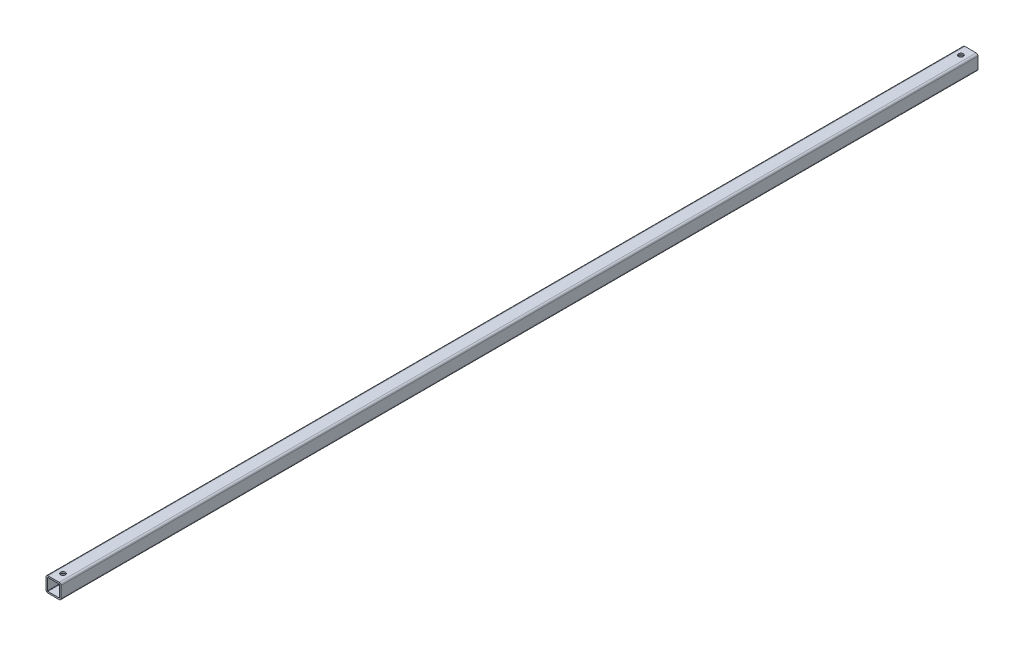
SolidWorks part; units mm, degrees
material "6063-T4"
ref_plane "Front Plane" through (0, 0, 0) normal (0, 0, 1) x (1, 0, 0)
ref_plane "Top Plane" through (0, 0, 0) normal (0, 1, 0) x (1, 0, 0)
ref_plane "Right Plane" through (0, 0, 0) normal (1, 0, 0) x (0, 0, -1)
sketch "Sketch1" plane through (0, 0, 0) normal (0, 0, 1) x (1, 0, 0)
  line L1 (7.5, -10) -> (-7.5, -10)
  line L2 (10, -7.5) -> (10, 7.5)
  line L3 (7.5, 10) -> (-7.5, 10)
  line L4 (-10, -7.5) -> (-10, 7.5)
  line L5 (10, -10) -> (-10, 10) construction
  line L6 (10, 10) -> (-10, -10) construction
  arc A0 (-7.5, 10) -> (-10, 7.5) centre (-7.5, 7.5) ccw
  arc A1 (10, 7.5) -> (7.5, 10) centre (7.5, 7.5) ccw
  arc A2 (7.5, -10) -> (10, -7.5) centre (7.5, -7.5) ccw
  arc A3 (-7.5, -10) -> (-10, -7.5) centre (-7.5, -7.5) cw
  point P0 (0, 0)
  dimension "D2" = 2.5
  dimension "D1" = 20
extrude "Extrude-Thin1" add sketch "Sketch1" along normal mid plane 1219.2 thin thin type one direction reverse wall 2
hole_wizard "1/4 (0.25) Diameter Hole1" positions "Sketch2" profile "Sketch3" hole size "1/4" standard "ANSI Inch"
sketch "Sketch2" plane through (0, 10, 0) normal (0, 1, 0) x (1, 0, 0)
  point P0 (0, 596.9)
sketch "Sketch3" plane through (0, 10, -596.9) normal (1, 0, 0) x (0, 0, 1)
  line L0 (0, 0) -> (0, 27.3077)
  line L1 (0, 27.3077) -> (3.175, 25.4)
  line L2 (3.175, 25.4) -> (3.175, 0)
  line L5 (3.175, 0) -> (0, 0)
  line L10 (0, 27.3077) -> (-3.175, 25.4) construction
  line L11 (0, -6.35) -> (0, 107.95) construction
  dimension "Hole Dia." = 6.35
  dimension "Hole Depth" = 25.4
  dimension "Drill Angle" = 118
hole_wizard "1/4 (0.25) Diameter Hole2" positions "Sketch4" profile "Sketch5" hole size "1/4" standard "ANSI Inch"
sketch "Sketch4" plane through (0, 10, 0) normal (0, 1, 0) x (1, 0, 0)
  point P0 (0, -596.9)
sketch "Sketch5" plane through (0, 10, 596.9) normal (1, 0, 0) x (0, 0, 1)
  line L0 (0, 0) -> (0, 27.3077)
  line L1 (0, 27.3077) -> (3.175, 25.4)
  line L2 (3.175, 25.4) -> (3.175, 0)
  line L5 (3.175, 0) -> (0, 0)
  line L10 (0, 27.3077) -> (-3.175, 25.4) construction
  line L11 (0, -6.35) -> (0, 107.95) construction
  dimension "Hole Dia." = 6.35
  dimension "Hole Depth" = 25.4
  dimension "Drill Angle" = 118
equation "\"D2@Sketch1\" = \"D5@Extrude-Thin1\" * 1.25"
